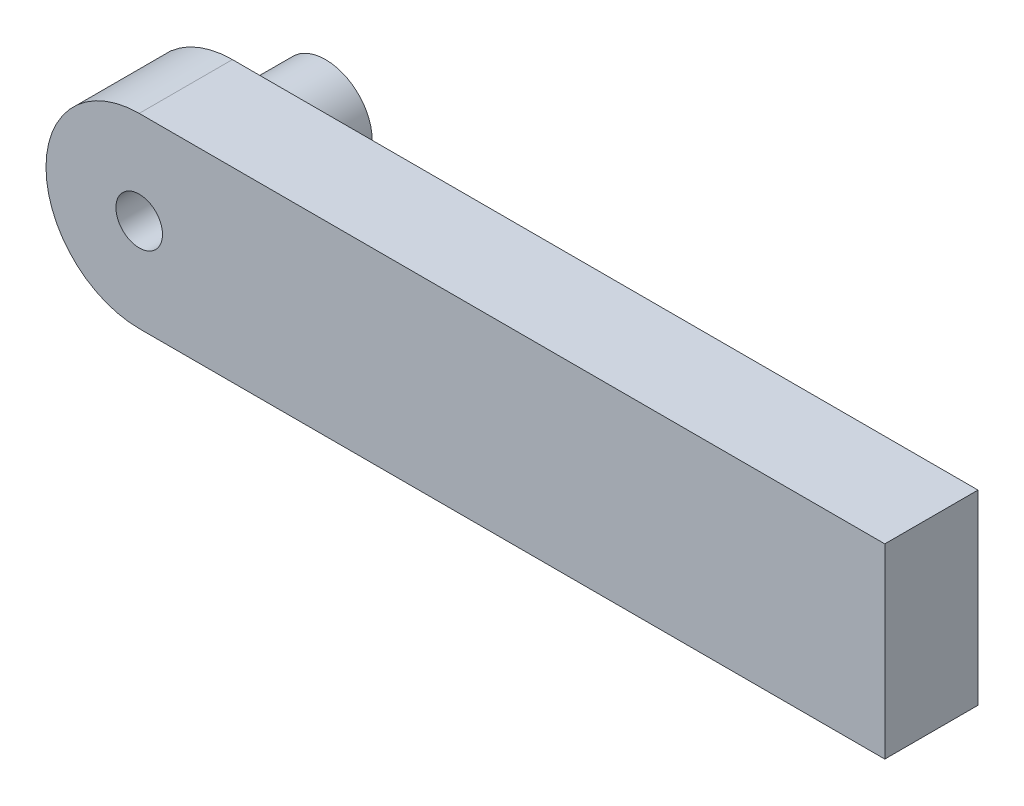
SolidWorks part; units mm, degrees
other "Videocamera1"
material "PET"
ref_plane "Piano frontale" through (0, 0, 0) normal (0, 0, 1) x (1, 0, 0)
ref_plane "Piano superiore" through (0, 0, 0) normal (0, 1, 0) x (1, 0, 0)
ref_plane "Piano destro" through (0, 0, 0) normal (1, 0, 0) x (0, 0, -1)
sketch "Schizzo1" plane through (0, 0, 0) normal (0, 0, 1) x (1, 0, 0)
  line L0 (20, 4.5035) -> (-20, 4.5035)
  line L2 (-20, -5.4965) -> (20, -5.4965)
  line L12 (20, 4.5035) -> (20, -5.4965)
  arc A0 (-20, 4.5035) -> (-20, -5.4965) centre (-20, -0.4965) ccw
  dimension "D1" = 10
  dimension "D9" = 40
extrude "Estrusione-Estrusione1" add sketch "Schizzo1" along normal blind 5
sketch "Schizzo2" plane through (0, 0, 0) normal (0, 0, -1) x (-1, 0, 0)
  arc A0 (20, -5.4965) -> (20, 4.5035) centre (20, -0.4965) ccw construction
  arc A1 (20, -5.4965) -> (20, 4.5035) centre (20, -0.4965) ccw construction
  circle A2 centre (20, -0.4965) radius 2.5
extrude "Estrusione-Estrusione2" add sketch "Schizzo2" along normal blind 5 contours A2
sketch "Schizzo3" plane through (0, 0, -5) normal (0, 0, -1) x (-1, 0, 0)
  circle A0 centre (20, -0.4965) radius 1.25
  dimension "D1" = 2.5
extrude "Taglio-Estrusione1" cut sketch "Schizzo3" against normal through all
ref_point "Punto1"
ref_axis "Assi1" through (-20, -0.4965, 5) along (0, 0, -1)
ref_axis "Assi2" through (20, 4.5035, 0) along (-1, 0, 0)
sketch "Schizzo4" plane through (0, 0, 0) normal (0, 0, -1) x (-1, 0, 0)
  line L0 (20, -0.4965) -> (2.37, -0.4965)
  dimension "D1" = 17.63
ref_plane "Piano1" through (-2.37, 0, 0) normal (1, 0, 0) x (0, 0, -1)
sketch "Schizzo5" plane through (-2.37, 0, 0) normal (1, 0, 0) x (0, 0, -1)
  line L0 (0, -0.4965) -> (-2.34, -0.4965)
  dimension "D1" = 2.34
